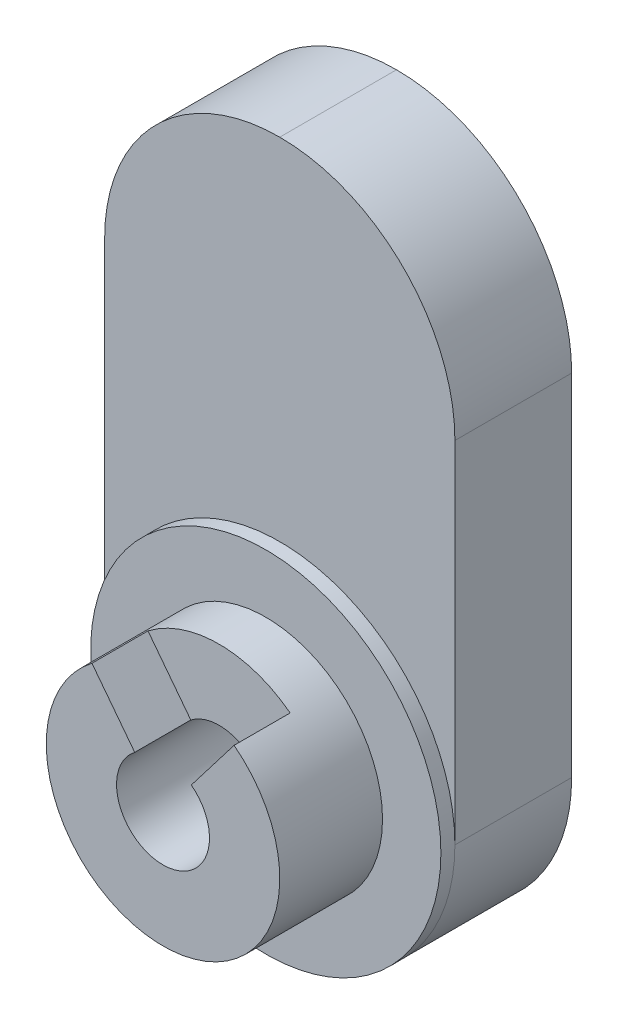
SolidWorks part; units mm, degrees
ref_plane "Front Plane" through (0, 0, 0) normal (0, 0, 1) x (1, 0, 0)
ref_plane "Top Plane" through (0, 0, 0) normal (0, 1, 0) x (1, 0, 0)
ref_plane "Right Plane" through (0, 0, 0) normal (1, 0, 0) x (0, 0, -1)
sketch "Sketch1" plane through (0, 0, 0) normal (0, 0, 1) x (1, 0, 0)
  line L1 (-9.525, 0) -> (9.525, 0)
  line L2 (-9.525, 0) -> (-9.525, 38.1)
  line L3 (-9.525, 38.1) -> (9.525, 38.1)
  line L4 (9.525, 0) -> (9.525, 38.1)
  point P4 (0, 0)
  dimension "D1" = 38.1
  dimension "D2" = 19.05
extrude "Boss-Extrude1" add sketch "Sketch1" along normal blind 6.35
sketch "Sketch2" plane through (0, 0, 6.35) normal (0, 0, 1) x (1, 0, 0)
  line L3 (-9.525, 0) -> (9.525, 0) construction
  circle A0 centre (0, 9.525) radius 6.35
  dimension "D1" = 12.7
  dimension "D2" = 9.525
extrude "Boss-Extrude2" add sketch "Sketch2" along normal blind 6.35
hole_wizard "#8 (0.199) Diameter Hole1" positions "Sketch3" profile "Sketch4" hole size "#8" standard "ANSI Inch" end condition through all
sketch "Sketch3" plane through (0, 0, 12.7) normal (0, 0, 1) x (1, 0, 0)
  circle A0 centre (0, 9.525) radius 6.35 construction
  point P0 (0, 9.525)
sketch "Sketch4" plane through (0, 9.525, 12.7) normal (1, 0, 0) x (0, -1, 0)
  line L0 (0, 0) -> (0, 12.7)
  line L1 (0, 12.7) -> (2.5273, 12.7)
  line L2 (2.5273, 12.7) -> (2.5273, 0)
  line L5 (2.5273, 0) -> (0, 0)
  line L11 (0, -6.35) -> (0, 107.95) construction
  dimension "Thru Hole Dia." = 5.0546
  dimension "Thru Hole Depth" = 12.7
sketch "Sketch5" plane through (0, 0, 0) normal (0, 0, -1) x (-1, 0, 0)
  line L1 (2.3464, 5.461) -> (4.6927, 9.525)
  line L2 (4.6927, 9.525) -> (2.3464, 13.589)
  line L3 (2.3464, 13.589) -> (-2.3464, 13.589)
  line L4 (-2.3464, 13.589) -> (-4.6927, 9.525)
  line L5 (-4.6927, 9.525) -> (-2.3464, 5.461)
  line L6 (-2.3464, 5.461) -> (2.3464, 5.461)
  circle A0 centre (0, 9.525) radius 4.064 construction
  dimension "D1" = 8.128
extrude "Cut-Extrude1" cut sketch "Sketch5" against normal blind 2.54
sketch "Sketch7" plane through (0, 0, 6.35) normal (0, 0, 1) x (1, 0, 0)
  circle A0 centre (0, 9.525) radius 9.525
  circle A1 centre (0, 9.525) radius 6.35
  circle A2 centre (0, 9.525) radius 6.35 construction
  dimension "D1" = 19.05
extrude "Boss-Extrude3" add sketch "Sketch7" along normal blind 0.762
sketch "Sketch8" plane through (0, 0, 12.7) normal (0, 0, 1) x (1, 0, 0)
  line L0 (1.5385, 11.53) -> (3.8656, 14.5628)
  line L1 (-3.8656, 14.5628) -> (-1.5385, 11.53)
  line L2 (-1.5385, 11.53) -> (0, 9.525) construction
  line L3 (0, 9.525) -> (1.5385, 11.53) construction
  arc A0 (3.8656, 14.5628) -> (-3.8656, 14.5628) centre (0, 9.525) ccw
  arc A1 (1.5385, 11.53) -> (-1.5385, 11.53) centre (0, 9.525) ccw
  circle A2 centre (0, 9.525) radius 2.5273 construction
  circle A3 centre (0, 9.525) radius 6.35 construction
  dimension "D1" = 75
extrude "Cut-Extrude2" cut sketch "Sketch8" against normal blind 3.048
fillet "Fillet1" radius 9.525 4 edges at (9.525, 0, 3.175) (-9.525, 0, 3.175) (9.525, 38.1, 3.175) (-9.525, 38.1, 3.175)
